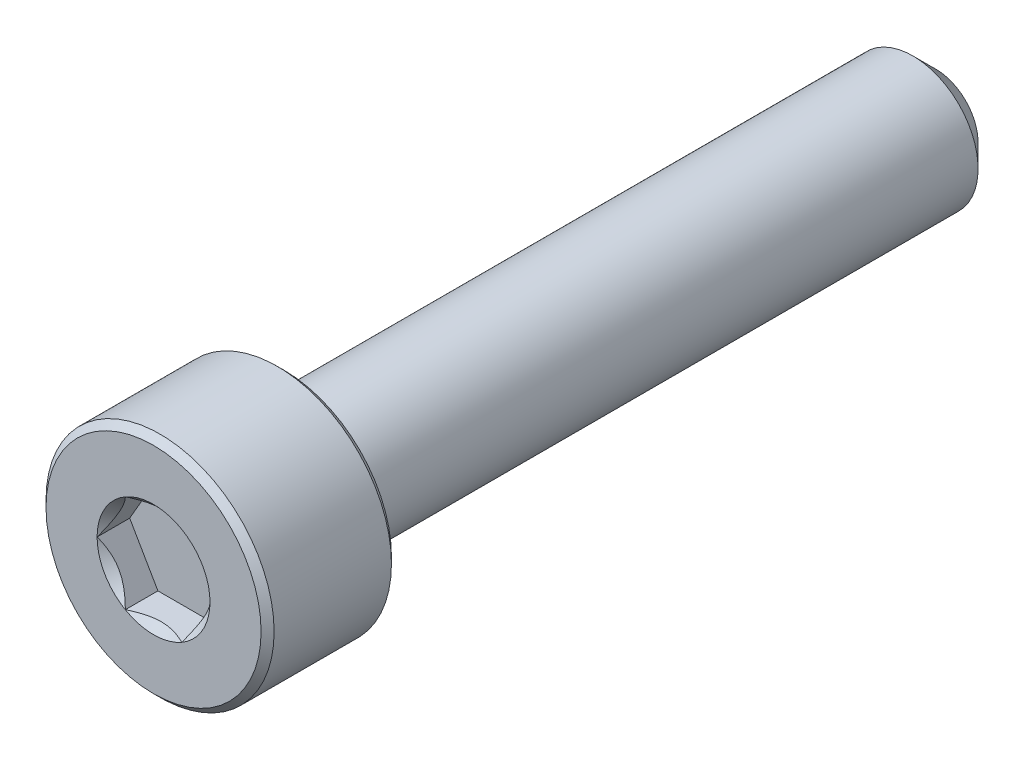
SolidWorks part; units mm, degrees
material "Alloy Steel"
ref_plane "Front Plane" through (0, 0, 0) normal (0, 0, 1) x (1, 0, 0)
ref_plane "Top Plane" through (0, 0, 0) normal (0, 1, 0) x (1, 0, 0)
ref_plane "Right Plane" through (0, 0, 0) normal (1, 0, 0) x (0, 0, -1)
sketch "Sketch1" plane through (0, 0, 0) normal (1, 0, 0) x (0, 0, -1)
  line L0 (-12, 0) -> (12, 0) construction
  line L1 (12, 0) -> (12, 1.3) construction
  line L2 (12, 1.3) -> (11.3, 2) construction
  line L3 (11.3, 2) -> (-6, 2) construction
  line L5 (-8, 2.25) -> (-8, 3.5) construction
  line L6 (-8, 3.5) -> (-12, 3.5) construction
  line L7 (-12, 3.5) -> (-12, 0) construction
  line L8 (12, 1.3) -> (12, 2) construction
  line L9 (11.9563, 2.0758) -> (12.3062, 1.4696) construction
  line L10 (12.3062, 1.4696) -> (12.6562, 2.0758) construction
  line L11 (12.6562, 2.0758) -> (11.9563, 2.0758) construction
  line L12 (12.3062, 2.0758) -> (12.3062, 2) construction
  line L13 (12.3062, 1.4696) -> (12.3062, 1.5453) construction
  line L14 (12.2625, 1.5453) -> (12.35, 1.5453) construction
  line L15 (12, 2) -> (12.6125, 2) construction
  line L16 (11.9781, 2.0379) -> (12.6344, 2.0379) construction
  line L17 (12, 0) -> (12, -2) construction
  line L18 (-8.2, 3.5) -> (-8, 3.3) construction
  line L19 (-11.8, 3.5) -> (-12, 3.3) construction
  point P0 (-12, 1.5)
  point P3 (9.55, 2)
  point P4 (0, 0)
  point P22 (12.3062, 1.5453)
  point P24 (-6, 2)
  point P25 (12.3062, 2)
  point P28 (12.3062, 2.0379)
  point P29 (9.55, -2)
  point P31 (-10, 3.5)
  point P37 (-8.7, 3.5)
  point P38 (-11.7, 3.5)
  dimension "head height" = 4
  dimension "D1" = 45
  dimension "head dia" = 7
  dimension "thread dia" = 4
  dimension "drive size" = 3
  dimension "pitch" = 0.7
  dimension "D2" = 0.0875
  dimension "D3" = 0.7
  dimension "D4" = 2.45
  dimension "D7" = 0.2
  dimension "D8" = 0.2
  dimension "D9" = 0.2
  dimension "D10" = 0.1
  dimension "D11" = 0.5
  dimension "D12" = 18
  dimension "length" = 20
sketch "Sketch2" plane through (0, 0, 0) normal (1, 0, 0) x (0, 0, -1)
  line L1 (-11.8, 3.5) -> (-8.2, 3.5)
  line L4 (11.3, 2) -> (12, 1.3)
  line L5 (12, 1.3) -> (12, 0)
  line L6 (-8.2, 3.5) -> (-8, 3.3) construction
  line L7 (12, 0) -> (-12, 0)
  line L8 (-11.8, 3.5) -> (-12, 3.3) construction
  line L9 (-8.2, 3.5) -> (-8, 3.3)
  line L10 (-11.8, 3.5) -> (-12, 3.3)
  line L11 (-12, 3.3) -> (-12, 0)
  line L12 (-8, 3.3) -> (-8, 2)
  line L13 (-8, 2) -> (11.3, 2)
revolve "Revolve1" add sketch "Sketch2" angle 360 about L7
sketch "Sketch3" plane through (0, 0, 12) normal (0, 0, 1) x (1, 0, 0)
  line L1 (0.866, 1.5) -> (-0.866, 1.5)
  line L2 (-0.866, 1.5) -> (-1.7321, 0)
  line L3 (-1.7321, 0) -> (-0.866, -1.5)
  line L4 (-0.866, -1.5) -> (0.866, -1.5)
  line L5 (0.866, -1.5) -> (1.7321, 0)
  line L6 (1.7321, 0) -> (0.866, 1.5)
  circle A0 centre (0, 0) radius 1.5 construction
extrude "Cut-Extrude1" cut sketch "Sketch3" against normal offset from surface (1 mm away) 1 up to face at (-3.3, 0, 12)
sketch "Sketch4" plane through (0, 0, 12) normal (0, 0, 1) x (1, 0, 0)
  circle A0 centre (0, 0) radius 1.7321
extrude "Cut-Extrude2" cut sketch "Sketch4" against normal blind 0.5 draft 45
ref_plane "Plane1" [suppressed] through (0, 0, 6) normal (0, 0, 1) x (1, 0, 0)
split "Split1" [suppressed] bodies to split 106
sketch "Sketch6" [suppressed] plane through (0, 0, -12) normal (0, 0, -1) x (-1, 0, 0)
  circle A0 centre (0, 0) radius 2
curve "Helix/Spiral1" [suppressed] pitch 0.7 height 20.7 turns 29.5714
sketch "Sketch7" [suppressed] plane through (0, 0, 0) normal (1, 0, 0) x (0, 0, -1)
  line L0 (11.9781, 2.0379) -> (12.6344, 2.0379)
  line L1 (12.6344, 2.0379) -> (12.35, 1.5453)
  line L2 (12.35, 1.5453) -> (12.2625, 1.5453)
  line L3 (12.2625, 1.5453) -> (11.9781, 2.0379)
sweep "Cut-Sweep1" [suppressed] cut profiles "Sketch7" path "Helix/Spiral1"
sketch "Sketch8" [suppressed] plane through (0, 0, 8) normal (0, 0, -1) x (-1, 0, 0)
  circle A0 centre (0, 0) radius 2
extrude "Boss-Extrude1" [suppressed] add sketch "Sketch8" along normal through all draft 45
ref_plane "Plane2" [suppressed] through (0, 0, 10) normal (0, 0, 1) x (1, 0, 0)
sketch "Sketch9" [suppressed] plane through (0, 0, 10) normal (0, 0, 1) x (1, 0, 0)
  line L0 (0, 3.325) -> (0.0611, 3.4995)
  line L1 (0, 3.325) -> (-0.0611, 3.4995)
  line L2 (0, 3.5) -> (0, 0) construction
  line L3 (-0.0611, 3.4995) -> (0, 0) construction
  line L4 (0, 0) -> (0.0611, 3.4995) construction
  arc A0 (0.0611, 3.4995) -> (-0.0611, 3.4995) centre (0, 0) ccw
  circle A1 centre (0, 0) radius 3.325 construction
  dimension "D2" = 6.65
  dimension "D3" = 2
extrude "Cut-Extrude4" [suppressed] cut sketch "Sketch9" against normal up to vertex and the other way up to vertex
pattern_circular "CirPattern2" [suppressed] count 175 over 360 about axis through (0, 0, 12) along (0, 0, -1) of bodies 113
equation "\"D2@Sketch1\"=\"pitch@Sketch1\"/8"
equation "\"D3@Sketch1\"=\"pitch@Sketch1\""
equation "\"D3@Helix/Spiral1\"=\"length@Sketch1\"+\"pitch@Sketch1\""
equation "\"D4@Helix/Spiral1\"=\"pitch@Sketch1\""
equation "\"D4@Sketch1\"=\"pitch@Sketch1\"*3.5"
equation "\"D7@Sketch1\"=\"head height@Sketch1\"*.05"
equation "\"D8@Sketch1\"=\"D7@Sketch1\""
equation "\"D9@Sketch1\"=\"D7@Sketch1\""
equation "\"D10@Sketch1\"=\"D7@Sketch1\"/2"
equation "\"D11@Sketch1\"=\"D10@Sketch1\"*5"
equation "\"D2@Sketch9\"=\"D1@Sketch9\"*.95"
equation "\"D1@CirPattern2\"= ( 360 / \"D3@Sketch9\" ) - 5"
